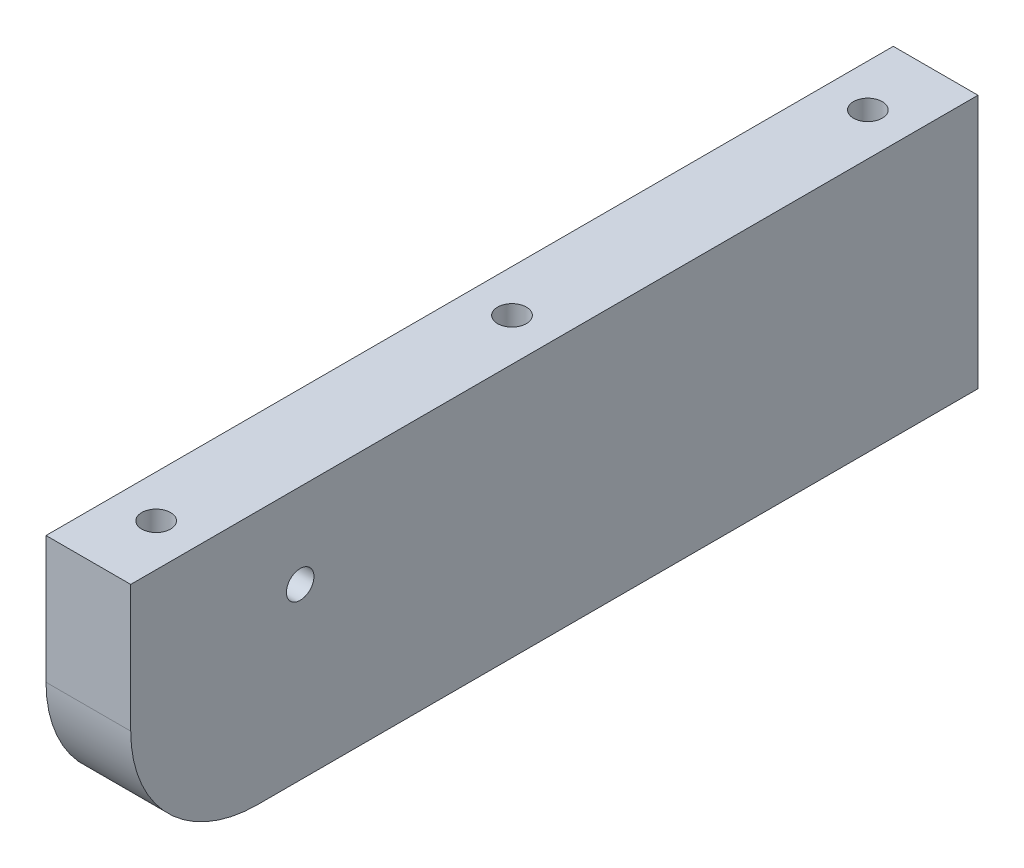
SolidWorks part; units mm, degrees
ref_plane "Front Plane" through (0, 0, 0) normal (0, 0, 1) x (1, 0, 0)
ref_plane "Top Plane" through (0, 0, 0) normal (0, 1, 0) x (1, 0, 0)
ref_plane "Right Plane" through (0, 0, 0) normal (1, 0, 0) x (0, 0, -1)
sketch "Sketch1" plane through (0, 0, 0) normal (1, 0, 0) x (0, 0, -1)
  line L1 (-50, -15) -> (50, -15)
  line L2 (-50, -15) -> (-50, 15)
  line L3 (-50, 15) -> (50, 15)
  line L4 (50, -15) -> (50, 15)
  line L5 (-50, -15) -> (50, 15) construction
  line L6 (-50, 15) -> (50, -15) construction
  circle A1 centre (-30, 5) radius 1.625
  point P0 (0, 0)
  dimension "D3" = 3.25
  dimension "D1" = 30
  dimension "D2" = 100
  dimension "D4" = 10
  dimension "D5" = 20
extrude "Boss-Extrude1" add sketch "Sketch1" along normal blind 10 contours L1 L4 L3 L2 region at (0, -0.0139, -0.0832)
fillet "Fillet1" radius 15 1 edges at (5, -15, 50)
hole_wizard "CBORE for M3 SHCS" positions "Sketch2" profile "Sketch3" counterbore size "M3" standard "ANSI Metric"
sketch "Sketch2" plane through (-616.2935, 25, -1323.2827) normal (0, 1, 0) x (1, 0, 0)
  line L3 (621.2935, -1281.2827) -> (621.2935, -1365.2827) construction
  line L5 (731.2935, -1281.2827) -> (731.2935, -1359.2827) construction
  circle A0 centre (731.2935, -1281.2827) radius 2.243
  circle A1 centre (731.2935, -1359.2827) radius 2.2384
  circle A3 centre (621.2935, -1281.2827) radius 2.3325
  circle A4 centre (621.2935, -1365.2827) radius 1.7576
  circle A5 centre (621.2935, -1323.2827) radius 1.8624
  circle A6 centre (731.2935, -1320.2827) radius 2.0271
  point P1 (731.2935, -1281.2827)
  point P8 (731.2935, -1359.2827)
  point P15 (621.2935, -1281.2827)
  point P17 (621.2935, -1365.2827)
  point P19 (621.2935, -1323.2827)
  point P27 (731.2935, -1320.2827)
  point P36 (0, 0)
sketch "Sketch3" plane through (115, 25, -42) normal (1, 0, 0) x (0, 0, 1)
  line L0 (0, 0) -> (0, 24.0215)
  line L1 (0, 24.0215) -> (1.7, 23)
  line L2 (1.7, 23) -> (1.7, 3)
  line L3 (1.7, 3) -> (3.25, 3)
  line L4 (3.25, 3) -> (3.25, 0)
  line L5 (3.25, 0) -> (0, 0)
  line L6 (0, 24.0215) -> (-1.7, 23) construction
  line L7 (0, -6.35) -> (0, 107.95) construction
  dimension "Hole Dia." = 3.4
  dimension "Hole Depth" = 23
  dimension "C'Bore Dia." = 6.5
  dimension "C'Bore Depth" = 3
  dimension "Drill Angle" = 118
